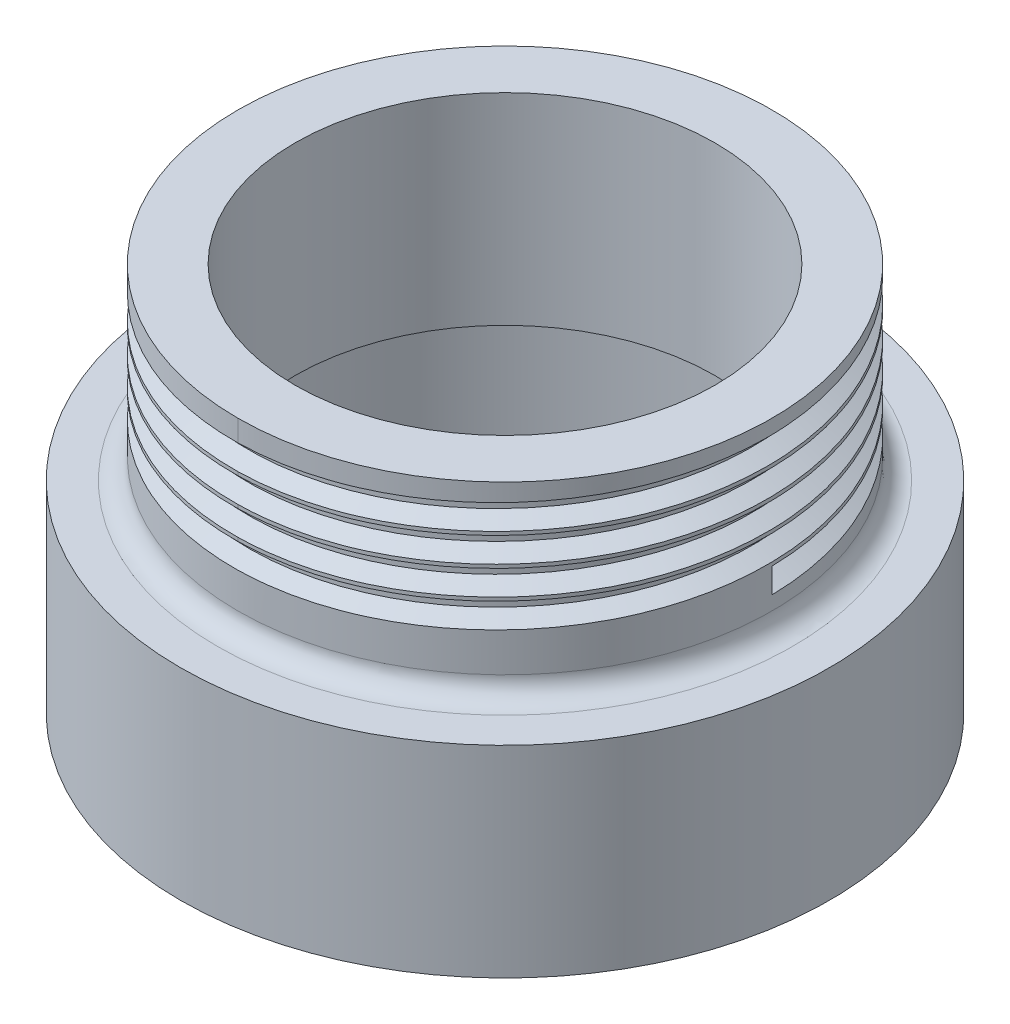
SolidWorks part; units mm, degrees
ref_plane "Front Plane" through (0, 0, 0) normal (0, 0, 1) x (1, 0, 0)
ref_plane "Top Plane" through (0, 0, 0) normal (0, 1, 0) x (1, 0, 0)
ref_plane "Right Plane" through (0, 0, 0) normal (1, 0, 0) x (0, 0, -1)
sketch "Sketch1" plane through (0, 0, 0) normal (0, 1, 0) x (1, 0, 0)
  circle A0 centre (0, 0) radius 16.0909
extrude "Boss-Extrude1" add sketch "Sketch1" along normal blind 19.2913
sketch "Sketch2" plane through (0, 19.2913, 0) normal (0, 1, 0) x (1, 0, 0)
  circle A0 centre (0, 0) radius 10.414
extrude "Cut-Extrude1" cut sketch "Sketch2" against normal through all and the other way through all
sketch "Sketch3" plane through (0, 0, 0) normal (0, -1, 0) x (1, 0, 0)
  circle A0 centre (0, 0) radius 12.7
extrude "Cut-Extrude2" cut sketch "Sketch3" against normal blind 9.2964
fillet "Fillet1" radius 1.016 1 edges at (0, 9.2964, -12.7)
sketch "Sketch6" plane through (0, 19.2913, 0) normal (0, 1, 0) x (1, 0, 0)
  circle A0 centre (0, 0) radius 13.2461
  circle A1 centre (0, 0) radius 16.0909
  dimension "D1" = 26.4922
extrude "Cut-Extrude4" cut sketch "Sketch6" against normal blind 9.2964
thread "Thread2" pitch 1.4111 method cut profile "Thread Profile3" start angle 0, offset 0, length 6.35, pitch 1.4111, diameter 26.4922
ref_plane "Plane3" through (-13.2461, 19.2913, 0) normal (0, 0, 1) x (-1, 0, 0)
sketch "Thread Profile3" plane through (-13.2461, 19.2913, 0) normal (0, 0, 1) x (-1, 0, 0)
  line L0 (0, 0) -> (0, 1.4111) construction
  line L11 (0, 0) -> (0, 1.2347)
  line L12 (0, 1.2347) -> (-0.7638, 0.7937)
  line L13 (-0.7638, 0.7937) -> (-0.7638, 0.441)
  line L15 (-0.7638, 0.441) -> (0, 0)
  line L17 (-0.7638, 0.6174) -> (0, 0.6174) construction
  point P2 (0, 0)
  dimension "Pitch" = 1.4111
  dimension "Profile_Angle" = 60
  dimension "Profile_Land" = 0.3528
  dimension "Profile_Height" = 0.7638
fillet "Fillet3" radius 1.016 1 edges at (0, 9.9949, 13.2461)
